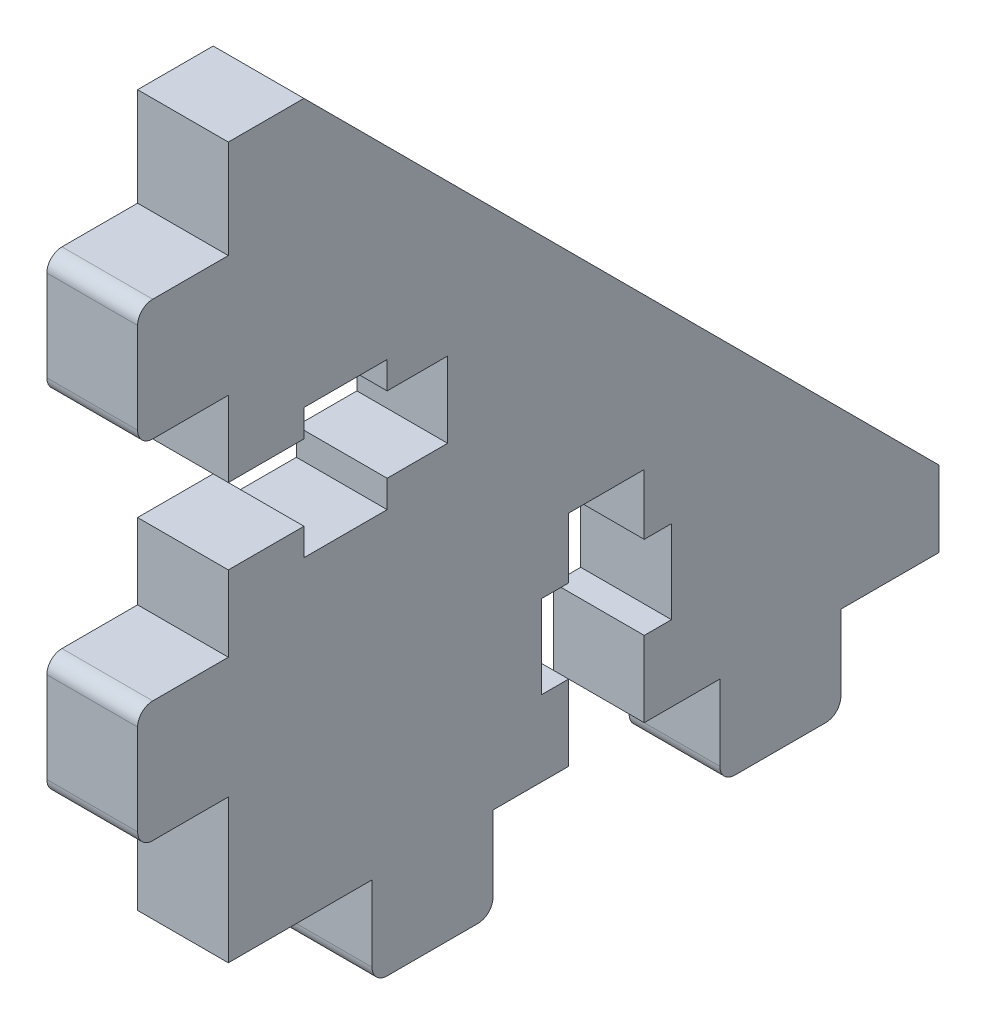
SolidWorks part; units mm, degrees
ref_plane "Plan de face" through (0, 0, 0) normal (0, 0, 1) x (1, 0, 0)
ref_plane "Plan de dessus" through (0, 0, 0) normal (0, 1, 0) x (1, 0, 0)
ref_plane "Plan de droite" through (0, 0, 0) normal (1, 0, 0) x (0, 0, -1)
sketch "Esquisse1" plane through (0, 0, 0) normal (1, 0, 0) x (0, -1, 0)
  line L0 (0, 0) -> (42, 42)
  line L1 (42, 42) -> (47, 42)
  line L2 (47, 42) -> (47, -5)
  line L3 (47, -5) -> (0, -5)
  line L4 (0, -5) -> (0, 0)
  line L5 (0, 0) -> (0, 30.772) construction
  dimension "D1" = 45
  dimension "D2" = 47
  dimension "D3" = 5
extrude "Boss.-Extru.1" add sketch "Esquisse1" along normal mid plane 6
sketch "Esquisse2" plane through (3, 0, 0) normal (1, 0, 0) x (0, -1, 0)
  line L0 (0, -5) -> (47, -5) construction
  line L1 (47, -5) -> (47, 42) construction
  line B0 (37.5, -5) -> (37.5, -10)
  line B1 (36.5, -11) -> (30.5, -11)
  line B2 (29.5, -10) -> (29.5, -5)
  line B3 (29.5, -5) -> (24.5, -5)
  line B4 (24.5, -5) -> (24.5, 0)
  line B5 (24.5, 0) -> (26.3, 0)
  line B6 (26.3, 0) -> (26.3, 5.5)
  line B7 (26.3, 5.5) -> (24.5, 5.5)
  line B8 (24.5, 5.5) -> (24.5, 9.5)
  line B9 (24.5, 9.5) -> (19.5, 9.5)
  line B10 (22, 9.5) -> (22, -5) construction
  line B11 (6.5, -5) -> (14.5, -5)
  line B12 (29.5, -5) -> (37.5, -5)
  line B13 (19.5, 5.5) -> (19.5, 9.5)
  line B14 (17.7, 5.5) -> (19.5, 5.5)
  line B15 (17.7, 0) -> (17.7, 5.5)
  line B16 (19.5, 0) -> (17.7, 0)
  line B17 (19.5, -5) -> (19.5, 0)
  line B18 (14.5, -5) -> (19.5, -5)
  line B19 (14.5, -10) -> (14.5, -5)
  line B20 (7.5, -11) -> (13.5, -11)
  line B21 (6.5, -5) -> (6.5, -10)
  line B22 (24.5, -5) -> (19.5, -5)
  arc B23 (30.5, -11) -> (29.5, -10) centre (30.5, -10) cw
  arc B24 (37.5, -10) -> (36.5, -11) centre (36.5, -10) cw
  arc B25 (6.5, -10) -> (7.5, -11) centre (7.5, -10) ccw
  arc B26 (13.5, -11) -> (14.5, -10) centre (13.5, -10) ccw
  line B27 (47, 35.5) -> (52, 35.5)
  line B28 (53, 34.5) -> (53, 28.5)
  line B29 (52, 27.5) -> (47, 27.5)
  line B30 (47, 27.5) -> (47, 22.5)
  line B31 (47, 22.5) -> (42, 22.5)
  line B32 (42, 22.5) -> (42, 24.3)
  line B33 (42, 24.3) -> (36.5, 24.3)
  line B34 (36.5, 24.3) -> (36.5, 22.5)
  line B35 (36.5, 22.5) -> (32.5, 22.5)
  line B36 (32.5, 22.5) -> (32.5, 17.5)
  line B37 (32.5, 20) -> (47, 20) construction
  line B38 (47, 4.5) -> (47, 12.5)
  line B39 (47, 27.5) -> (47, 35.5)
  line B40 (36.5, 17.5) -> (32.5, 17.5)
  line B41 (36.5, 15.7) -> (36.5, 17.5)
  line B42 (42, 15.7) -> (36.5, 15.7)
  line B43 (42, 17.5) -> (42, 15.7)
  line B44 (47, 17.5) -> (42, 17.5)
  line B45 (47, 12.5) -> (47, 17.5)
  line B46 (52, 12.5) -> (47, 12.5)
  line B47 (53, 5.5) -> (53, 11.5)
  line B48 (47, 4.5) -> (52, 4.5)
  line B49 (47, 22.5) -> (47, 17.5)
  arc B50 (53, 28.5) -> (52, 27.5) centre (52, 28.5) cw
  arc B51 (52, 35.5) -> (53, 34.5) centre (52, 34.5) cw
  arc B52 (52, 4.5) -> (53, 5.5) centre (52, 5.5) ccw
  arc B53 (53, 11.5) -> (52, 12.5) centre (52, 11.5) ccw
  dimension "D1" = 6.5
  dimension "D2" = 6.5
sketch_block_instance "Bloc-attache-male-1"
sketch_block "Bloc-attache-male" parameters "D7"=1, "D1"=5, "D2"=5, "D3"=5.5, "D4"=1.8, "D5"=4, "D6"=2.5
sketch_block_instance "Bloc-attache-male-2"
extrude "Boss.-Extru.2" add sketch "Esquisse2" against normal blind 6 contours B20 B26 B19 L1 B21 B25 | B24 B0 L1 B2 B23 B1 | B47 B53 B46 B0 B48 B52 | B51 B27 B0 B29 B50 B28 region at (3, -49.9749, -31.5) region at (3, -49.9749, -8.5) region at (3, -10.5, 7.9749) region at (3, -33.5, 7.9749)
extrude "Enlèv. mat.-Extru.1" cut sketch "Esquisse2<3>" against normal blind 6 contours B17 L1 B4 B5 B6 B7 B8 B9 B13 B14 B15 B16 | B44 B0 B31 B32 B33 B34 B35 B36 B40 B41 B42 B43 region at (3, -39.6427, -20) region at (3, -22, -2.3573)
sketch "Esquisse2<3>" plane through (3, 0, 0) normal (1, 0, 0) x (0, -1, 0) same geometry as "Esquisse2"
